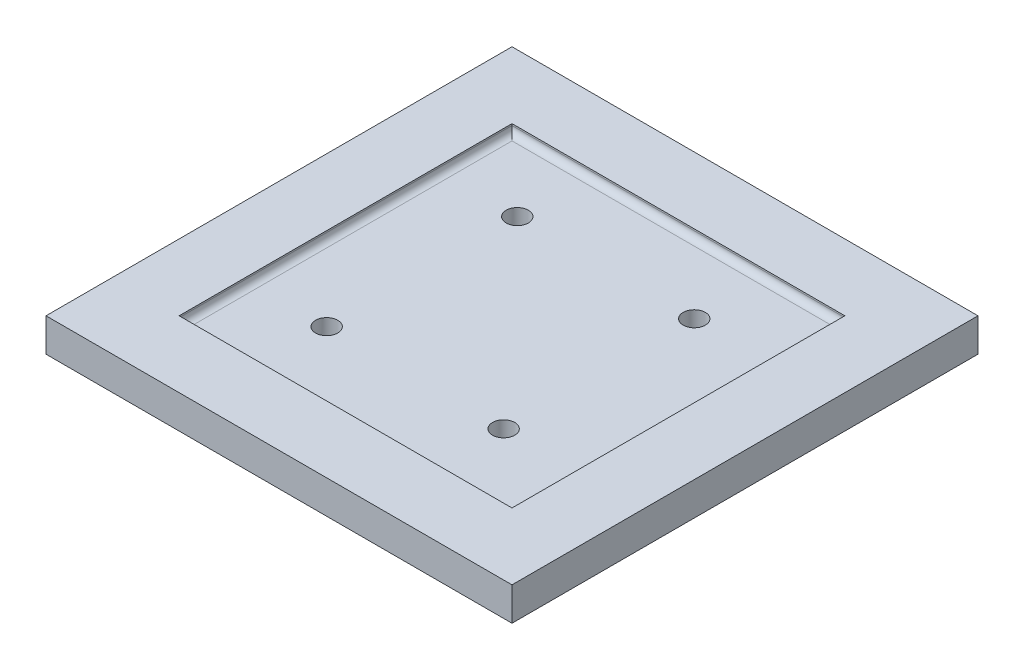
SolidWorks part; units mm, degrees
ref_plane "Front Plane" through (0, 0, 0) normal (0, 0, 1) x (1, 0, 0)
ref_plane "Top Plane" through (0, 0, 0) normal (0, 1, 0) x (1, 0, 0)
ref_plane "Right Plane" through (0, 0, 0) normal (1, 0, 0) x (0, 0, -1)
sketch "Sketch10" plane through (0, 0, 0) normal (0, 1, 0) x (1, 0, 0)
  line L1 (88.9, -88.9) -> (-88.9, -88.9)
  line L2 (88.9, -88.9) -> (88.9, 88.9)
  line L3 (88.9, 88.9) -> (-88.9, 88.9)
  line L4 (-88.9, -88.9) -> (-88.9, 88.9)
  line L5 (88.9, -88.9) -> (-88.9, 88.9) construction
  line L6 (88.9, 88.9) -> (-88.9, -88.9) construction
  point P0 (0, 0)
  dimension "D1" = 177.8
  dimension "D2" = 177.8
extrude "Boss-Extrude4" add sketch "Sketch10" along normal blind 12.7 contours L2 L1 L4 L3
sketch "Sketch12" plane through (0, 12.7, 0) normal (0, 1, 0) x (1, 0, 0)
  line L1 (63.5, -63.5) -> (-63.5, -63.5)
  line L2 (63.5, -63.5) -> (63.5, 63.5)
  line L3 (63.5, 63.5) -> (-63.5, 63.5)
  line L4 (-63.5, -63.5) -> (-63.5, 63.5)
  line L5 (63.5, -63.5) -> (-63.5, 63.5) construction
  line L6 (63.5, 63.5) -> (-63.5, -63.5) construction
  point P1 (0, 0)
  dimension "D1" = 127
  dimension "D2" = 127
extrude "Boss-Extrude5" add sketch "Sketch12" against normal blind 3.175
sketch "Sketch13" plane through (0, 12.7, 0) normal (0, 1, 0) x (1, 0, 0)
  line L1 (63.5, -63.5) -> (-63.5, -63.5)
  line L2 (63.5, -63.5) -> (63.5, 63.5)
  line L3 (63.5, 63.5) -> (-63.5, 63.5)
  line L4 (-63.5, -63.5) -> (-63.5, 63.5)
  line L5 (63.5, -63.5) -> (-63.5, 63.5) construction
  line L6 (63.5, 63.5) -> (-63.5, -63.5) construction
  point P0 (0, 0)
  dimension "D1" = 127
  dimension "D2" = 127
extrude "Cut-Extrude1" cut sketch "Sketch13" against normal blind 3.175
sketch "Sketch14" plane through (0, 0, 0) normal (0, -1, 0) x (-1, 0, 0)
  line L1 (63.5, -63.5) -> (-63.5, -63.5)
  line L2 (63.5, -63.5) -> (63.5, 63.5)
  line L3 (63.5, 63.5) -> (-63.5, 63.5)
  line L4 (-63.5, -63.5) -> (-63.5, 63.5)
  line L5 (63.5, -63.5) -> (-63.5, 63.5) construction
  line L6 (63.5, 63.5) -> (-63.5, -63.5) construction
  point P0 (0, 0)
  dimension "D1" = 127
  dimension "D2" = 127
extrude "Cut-Extrude2" cut sketch "Sketch14" against normal blind 3.175
fillet "Fillet4" radius 2.54 8 edges at (-63.5, 9.525, 0) (0, 9.525, 63.5) (0, 9.525, -63.5) (63.5, 9.525, 0) (0, 3.175, 63.5) (-63.5, 3.175, 0) (0, 3.175, -63.5) (63.5, 3.175, 0)
sketch "Sketch16" plane through (0, 9.525, 0) normal (0, 1, 0) x (1, 0, 0)
  circle A0 centre (-34.9456, 36.9526) radius 2.794
  circle A1 centre (32.5844, 36.9526) radius 2.794
  circle A2 centre (-34.9456, -35.772) radius 2.794
  circle A3 centre (32.5844, -35.772) radius 2.794
  dimension "D1" = 5.588
extrude "Cut-Extrude3" cut sketch "Sketch16" against normal blind 25.4
scale "Scale1" bodies to scale 108 scale about centroid uniform scaling yes scale factor 0.75
sketch "Sketch17" plane through (0, 8.7312, 0) normal (0, 1, 0) x (1, 0, 0)
  circle A0 centre (-26.2086, 27.7141) radius 3.175
  circle A1 centre (24.4389, 27.7141) radius 3.175
  circle A2 centre (-26.2086, -26.8293) radius 3.175
  circle A3 centre (24.4389, -26.8293) radius 3.175
extrude "Cut-Extrude5" cut sketch "Sketch17" against normal blind 15.748
